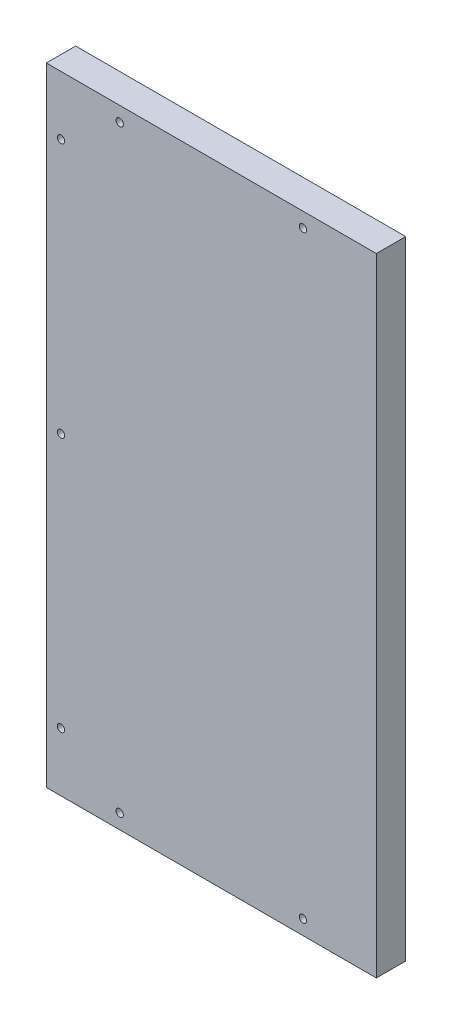
SolidWorks part; units mm, degrees
material "Beech"
ref_plane "Front Plane" through (0, 0, 0) normal (0, 0, 1) x (1, 0, 0)
ref_plane "Top Plane" through (0, 0, 0) normal (0, 1, 0) x (1, 0, 0)
ref_plane "Right Plane" through (0, 0, 0) normal (1, 0, 0) x (0, 0, -1)
sketch "Sketch1" plane through (0, 0, 0) normal (0, 0, 1) x (1, 0, 0)
  line L0 (-234.753, 19.05) -> (-234.753, 0) construction
  line L1 (-234.753, 82.8417) -> (-91.9973, 82.8417)
  line L2 (-234.753, 82.8417) -> (-234.753, -188.5238)
  line L3 (-234.753, -188.5238) -> (-91.9973, -188.5238)
  line L4 (-91.9973, 82.8417) -> (-91.9973, -188.5238)
extrude "Boss-Extrude1" add sketch "Sketch1" along normal blind 12.7
hole_wizard "Hole1" positions "Sketch2" profile "Sketch3" legacy
sketch "Sketch2" plane through (181.0394, -52.975, 0) normal (0, 0, -1) x (0, -1, 0)
  line L0 (-129.4667, 415.7924) -> (-129.4667, 273.0368) construction
  line L5 (-135.8167, 409.4424) -> (135.5488, 409.4424) construction
  line L10 (-135.8167, 279.3868) -> (135.5488, 279.3868) construction
  line L11 (-0.134, 409.4424) -> (-0.134, 279.3868) construction
  point P22 (-129.4667, 384.0424)
  point P24 (-129.4667, 304.7868)
  point P26 (-110.4167, 409.4424)
  point P30 (-0.134, 409.4424)
  point P50 (110.1488, 409.4424)
  point P51 (129.1988, 304.7868)
  point P52 (129.1988, 384.0424)
sketch "Sketch3" plane through (-203.003, -182.1738, 0) normal (1, 0, 0) x (0, 1, 0)
  line L0 (0, 0) -> (0, 32.7039)
  line L1 (0, 32.7039) -> (1.5875, 31.75)
  line L2 (1.5875, 31.75) -> (1.5875, 4.0177)
  line L3 (1.5875, 4.0177) -> (5.08, 0)
  line L4 (5.08, 0) -> (0, 0)
  line L5 (0, -14.3089) -> (0, 102.4216) construction
  line L6 (0, 32.7039) -> (-1.5875, 31.75) construction
  line L7 (-1.5875, 4.0177) -> (-5.08, 0) construction
  dimension "Diameter" = 3.175
  dimension "Depth" = 31.75
  dimension "C-Sink Diameter" = 10.16
  dimension "C-Sink Angle" = 82
  dimension "Drill Angle" = 118
